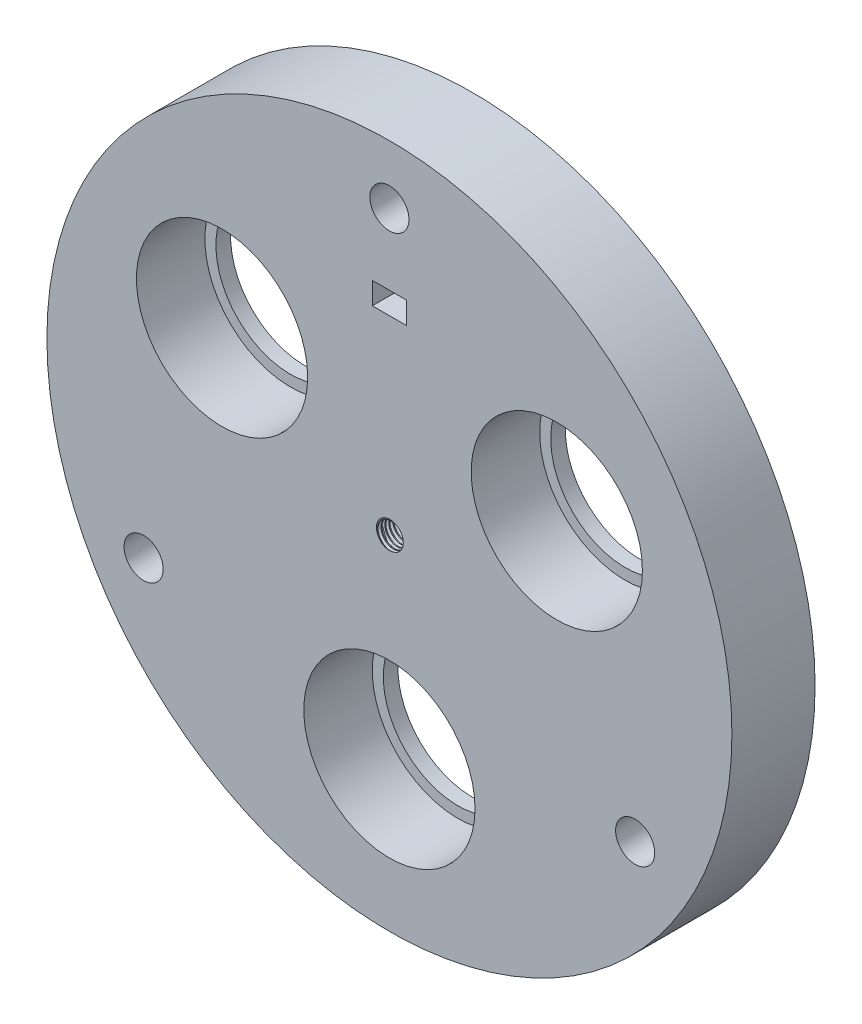
SolidWorks part; units mm, degrees
material "6063-T6"
ref_plane "Plano frontal" through (0, 0, 0) normal (0, 0, 1) x (1, 0, 0)
ref_plane "Plano superior" through (0, 0, 0) normal (0, 1, 0) x (1, 0, 0)
ref_plane "Plano direito" through (0, 0, 0) normal (1, 0, 0) x (0, 0, -1)
sketch "Esboço1" plane through (0, 0, 0) normal (0, 0, 1) x (1, 0, 0)
  line L0 (-34.208, 19.75) -> (0, 0) construction
  line L1 (0, 0) -> (34.208, 19.75) construction
  line L2 (0, 0) -> (0, -39.5) construction
  circle A0 centre (0, 0) radius 70
  circle A5 centre (0, -39.5) radius 17.5
  circle A6 centre (-34.208, 19.75) radius 17.5
  circle A7 centre (34.208, 19.75) radius 17.5
  point P11 (0, 0)
  dimension "D1" = 140
  dimension "D2" = 35
  dimension "D4" = 3
  dimension "D3" = 39.5
extrude "Ressalto-extrusão1" add sketch "Esboço1" along normal blind 17
sketch "Esboço15" plane through (0, 0, 0) normal (0, 0, 1) x (1, 0, 0)
  circle A6 centre (0, -39.5) radius 17.5
  circle A7 centre (0, -39.5) radius 15.25
  circle A8 centre (-34.208, 19.75) radius 15.25
  circle A9 centre (-34.208, 19.75) radius 17.5
  circle A10 centre (34.208, 19.75) radius 15.25
  circle A11 centre (34.208, 19.75) radius 17.5
  point P15 (0, 0)
  dimension "D1" = 35
  dimension "D2" = 30.5
  dimension "D3" = 3
  dimension "D4" = 39.5
  dimension "D5" = 39.5
extrude "Ressalto-extrusão5" add sketch "Esboço15" along normal blind 3
sketch "Esboço17" plane through (0, 0, 0) normal (0, 0, -1) x (-1, 0, 0)
  circle A1 centre (0, 58) radius 4
  circle A2 centre (50.2295, -29) radius 4
  circle A3 centre (-50.2295, -29) radius 4
  point P12 (0, 0)
  dimension "D1" = 8
  dimension "D2" = 58
  dimension "D3" = 3
extrude "Corte-extrusão1" cut sketch "Esboço17" against normal through all both and the other way through all
sketch "Esboço18" plane through (0, 0, 17) normal (0, 0, 1) x (1, 0, 0)
  circle A0 centre (0, 0) radius 3
  dimension "D1" = 6
extrude "Corte-extrusão2" cut sketch "Esboço18" against normal through all both and the other way through all
thread "Rosca1" pitch 0.8 method extrude trim with start face yes trim with end face yes profile "Perfil da rosca1" start angle 0, offset 1, length 0, pitch 0.8, diameter 6
ref_plane "Plano1" through (-3, 0, 18) normal (0, -1, 0) x (-1, 0, 0)
sketch "Perfil da rosca1" plane through (-3, 0, 18) normal (0, -1, 0) x (-1, 0, 0)
  line L0 (0, 0) -> (0, 0.8) construction
  line L11 (0, 0) -> (0, 0.7)
  line L12 (0, 0.7) -> (-0.433, 0.45)
  line L13 (-0.433, 0.45) -> (-0.433, 0.25)
  line L15 (-0.433, 0.25) -> (0, 0)
  line L17 (-0.433, 0.35) -> (0, 0.35) construction
  point P2 (0, 0)
  dimension "Pitch" = 0.8
  dimension "Profile_Angle" = 60
  dimension "Profile_Land" = 0.2
  dimension "Profile_Height" = 0.433
sketch "Esboço19" plane through (0, 0, 17) normal (0, 0, 1) x (1, 0, 0)
  circle A0 centre (0, 0) radius 20
  dimension "D1" = 40
sketch "Esboço20" plane through (0, 0, 17) normal (0, 0, 1) x (1, 0, 0)
  line L1 (3.5, 43.5) -> (-3.5, 43.5)
  line L2 (3.5, 43.5) -> (3.5, 39)
  line L3 (3.5, 39) -> (-3.5, 39)
  line L4 (-3.5, 43.5) -> (-3.5, 39)
  line L5 (3.5, 43.5) -> (-3.5, 39) construction
  line L6 (3.5, 39) -> (-3.5, 43.5) construction
  point P0 (0, 41.25)
  dimension "D1" = 7
  dimension "D2" = 4.5
extrude "Corte-extrusão3" cut sketch "Esboço20" against normal through all both and the other way through all
